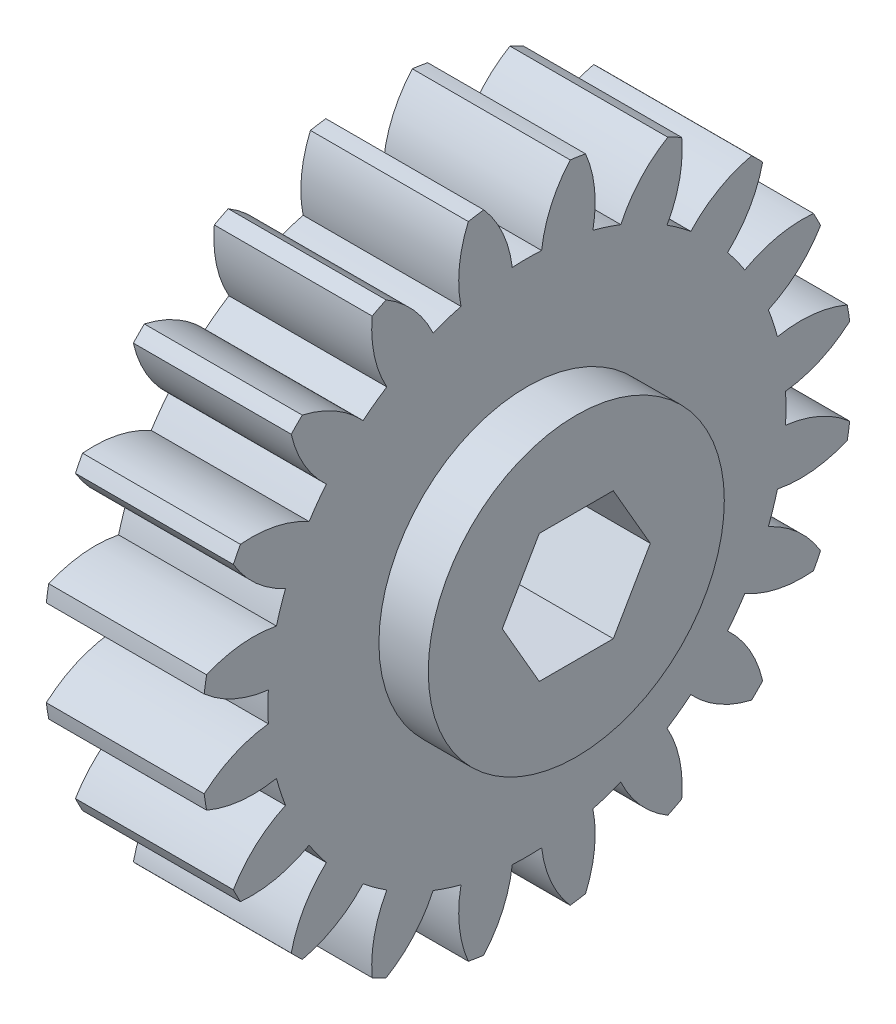
SolidWorks part; units mm, degrees
ref_plane "Plane1" through (0, 0, 0) normal (0, 0, 1) x (1, 0, 0)
ref_plane "Plane2" through (0, 0, 0) normal (0, 1, 0) x (1, 0, 0)
ref_plane "Plane3" through (0, 0, 0) normal (1, 0, 0) x (0, 0, -1)
sketch "HoldingSke" plane through (0, 0, 0) normal (0, 1, 0) x (1, 0, 0)
  line L0 (0, 0) -> (0.6265, -0.228)
  line L1 (-15, 0) -> (100, 0) construction
  line L2 (0, 0) -> (-2.1039, 2.3779)
  line L3 (0, 0) -> (-11.863, 4.5341)
  line L4 (0, 0) -> (8.1152, 2.9537)
  line L5 (0, 0) -> (-46.8476, -17.4728)
  line L6 (0, 0) -> (-9.9476, -6.7116)
  line L7 (-2.1039, 2.3779) -> (8.6586, 51.2059)
  line L8 (-76.2, 54.61) -> (-75.3, 54.61)
  line L9 (-71.009, 38.7566) -> (-53.1078, 45.2721)
  line L10 (-76.2, 71.12) -> (104.1128, 71.12)
  line L11 (0, 0) -> (-12, 0)
  line L12 (-76.2, 101.6) -> (-76.147, 101.6)
  line L13 (24.9733, 27.94) -> (52.9518, 28.4284)
  line L14 (24.9733, 27.94) -> (24.9743, 27.94)
  line L15 (24.9733, 27.94) -> (100.4006, 29.5858)
  line L16 (-63.627, -1.5) -> (-12.827, -1.5)
  circle A0 centre (0, 0) radius 2.5
  circle A1 centre (0, 0) radius 13.124
  circle A2 centre (0, 0) radius 37.5
  circle A3 centre (0, 0) radius 2.5
  dimension "MHD" = 26.248
  dimension "Hub_dia" = 75
  dimension "Bore" = 5
  dimension "MBD" = 5
  dimension "Num_teeth" = 20
  dimension "Pitch" = 0.6667
  dimension "Overall_len" = 50
  dimension "Show_teeth" = 20
  dimension "Thickness" = 12
  dimension "OAL" = 50.0001
  dimension "T_dim" = 0.9
  dimension "Ap" = 20
  dimension "H" = 19.05
  dimension "Pitch_radius" = 180.3128
  dimension "Width" = 12
  dimension "Backlash" = 0.053
  dimension "Addendum_fac" = 1
  dimension "Dedendum_fac" = 1.25
  dimension "Clearance_fac" = 0.25
  dimension "Dedendum_add" = 0.001
  dimension "Module" = 1.5
sketch "BasProSke" plane through (0, 0, 0) normal (0, 1, 0) x (1, 0, 0)
  line L0 (-10, 0) -> (60, 0) construction
  line L1 (0, 0) -> (0, 16.5)
  line L2 (0, 0) -> (8, 0)
  line L3 (8, 0) -> (8, 16.5)
  line L4 (8, 16.5) -> (0, 16.5)
  dimension "Thickness" = 8
  dimension "Diameter" = 33
revolve "Base-Revolve" add sketch "BasProSke" angle 360 about L0
sketch "TooCutSke" plane through (0, 0, 0) normal (1, 0, 0) x (0, 0, -1)
  line L1 (0, 0) -> (0, 107) construction
  line L2 (0, 0) -> (-1.2696, 14.9462) construction
  line L3 (0, 0) -> (-4.6808, 29.5532) construction
  line L4 (-1.2696, 14.9462) -> (-2.3404, 14.7766) construction
  arc A0 (0.7438, 13.1029) -> (-0.7438, 13.1029) centre (0, 0) ccw
  arc A1 (2.21, 16.377) -> (-2.21, 16.377) centre (0, 0) ccw
  circle A2 centre (0, 0) radius 15 construction
  circle A3 centre (0, 0) radius 14.0954 construction
  arc A4 (-0.7438, 13.1029) -> (-2.21, 16.377) centre (-6.7025, 12.3999) ccw
  arc A5 (2.21, 16.377) -> (0.7438, 13.1029) centre (6.7025, 12.3999) ccw
  dimension "Root_dia" = 26.248
  dimension "Overcut_dia" = 33.0508
  dimension "Pitch_dia" = 30
  dimension "Base_dia" = 28.1908
  dimension "Flank_rad" = 6
  dimension "Half_ang" = 9
  dimension "Half_CT" = 1.0841
extrude "ToothCut" cut sketch "TooCutSke" along normal through all
fillet "Breaks" [suppressed] radius 0.03 tangent propagation no
fillet "RootFillets" [suppressed] radius 0.376
pattern_circular "TeethCuts" count 20 every 18 about axis through (-10, 0, 0) along (1, 0, 0) of "ToothCut", "RootFillets", "Breaks"
sketch "HubNeaOneSke" plane through (0, 0, 0) normal (-1, 0, 0) x (0, 0, 1)
  circle A0 centre (0, 0) radius 13.124
  dimension "Diameter" = 26.248
extrude "HubNearOne" [suppressed] add sketch "HubNeaOneSke" along normal blind 42.0001
sketch "HubNeaBotSke" plane through (0, 0, 0) normal (-1, 0, 0) x (0, 0, 1)
  circle A0 centre (0, 0) radius 13.124
  dimension "Diameter" = 26.248
extrude "HubNearBoth" [suppressed] add sketch "HubNeaBotSke" along normal blind 21
ref_plane "FarPln" through (8, 0, 0) normal (1, 0, 0) x (0, 0, -1)
sketch "HubFarSke" plane through (8, 0, 0) normal (1, 0, 0) x (0, 0, -1)
  circle A0 centre (0, 0) radius 13.124
  dimension "Diameter" = 26.248
extrude "HubFar" [suppressed] add sketch "HubFarSke" along normal blind 21
sketch "BorSke" plane through (0, 0, 0) normal (1, 0, 0) x (0, 0, -1)
  circle A0 centre (0, 0) radius 2.5
  dimension "Diameter" = 5
extrude "Bore" cut sketch "BorSke" along normal mid plane 100.0001
sketch "KeySke" plane through (0, 0, 0) normal (1, 0, 0) x (0, 0, -1)
  line L0 (-1, 0) -> (-1, 3.4)
  line L1 (-1, 3.4) -> (1, 3.4)
  line L2 (1, 3.4) -> (1, 0)
  line L3 (0, 0) -> (0, 34) construction
  line L4 (-1, 0) -> (1, 0)
  dimension "Offset" = 3.4
  dimension "Width" = 2
extrude "Keyway" [suppressed] cut sketch "KeySke" along normal mid plane 100.0001
pattern_circular "Keyway2" [suppressed] count 2 every 90 about axis through (-10, 0, 0) along (1, 0, 0) reverse direction yes
sketch "Sketch1" plane through (8, 0, 0) normal (1, 0, 0) x (0, 0, -1)
  line L1 (3.75, 0) -> (1.875, 3.2476)
  line L2 (1.875, 3.2476) -> (-1.875, 3.2476)
  line L3 (-1.875, 3.2476) -> (-3.75, 0)
  line L4 (-3.75, 0) -> (-1.875, -3.2476)
  line L5 (-1.875, -3.2476) -> (1.875, -3.2476)
  line L6 (1.875, -3.2476) -> (3.75, 0)
  circle A0 centre (0, 0) radius 3.2476 construction
  circle A1 centre (0, 0) radius 3.75 construction
  dimension "D1" = 7.5
extrude "Cut-Extrude1" cut sketch "Sketch1" against normal through all
ref_plane "Plane4" through (8, 16.2303, -2.9711) normal (1, 0, 0) x (0, 0, -1)
sketch "Sketch2" plane through (8, 16.2303, -2.9711) normal (1, 0, 0) x (0, 0, -1)
  line L0 (-6.7211, -16.2303) -> (-4.8461, -19.4779) construction
  line L1 (-4.8461, -19.4779) -> (-1.0961, -19.4779) construction
  line L2 (-1.0961, -19.4779) -> (0.7789, -16.2303) construction
  line L3 (0.7789, -16.2303) -> (-1.0961, -12.9827) construction
  line L4 (-1.0961, -12.9827) -> (-4.8461, -12.9827) construction
  line L5 (-4.8461, -12.9827) -> (-6.7211, -16.2303) construction
  line L6 (-4.8461, -12.9827) -> (-6.7211, -16.2303)
  line L7 (-1.0961, -12.9827) -> (-4.8461, -12.9827)
  line L8 (0.7789, -16.2303) -> (-1.0961, -12.9827)
  line L9 (-1.0961, -19.4779) -> (0.7789, -16.2303)
  line L10 (-4.8461, -19.4779) -> (-1.0961, -19.4779)
  line L11 (-6.7211, -16.2303) -> (-4.8461, -19.4779)
  circle A0 centre (-2.9711, -16.2303) radius 7.5
  dimension "D1" = 15
extrude "Boss-Extrude1" add sketch "Sketch2" along normal blind 2.5
sketch "Sketch3" plane through (0, 0, 0) normal (-1, 0, 0) x (0, 0, 1)
  line L0 (1.875, 3.2476) -> (3.75, 0) construction
  line L1 (-1.875, 3.2476) -> (1.875, 3.2476) construction
  line L2 (-3.75, 0) -> (-1.875, 3.2476) construction
  line L3 (-1.875, -3.2476) -> (-3.75, 0) construction
  line L4 (1.875, -3.2476) -> (-1.875, -3.2476) construction
  line L5 (3.75, 0) -> (1.875, -3.2476) construction
  line L6 (3.75, 0) -> (1.875, -3.2476)
  line L7 (1.875, -3.2476) -> (-1.875, -3.2476)
  line L8 (-1.875, -3.2476) -> (-3.75, 0)
  line L9 (-3.75, 0) -> (-1.875, 3.2476)
  line L10 (-1.875, 3.2476) -> (1.875, 3.2476)
  line L11 (1.875, 3.2476) -> (3.75, 0)
  circle A0 centre (0, 0) radius 7.5
  dimension "D1" = 15
extrude "Boss-Extrude2" add sketch "Sketch3" along normal blind 2.5
equation "' \"Module@HoldingSke\" = 6.35"
equation "' \"Num_teeth@HoldingSke\" = 12"
equation "' \"Ap@HoldingSke\" =  20"
equation "' \"Ap@HoldingSke\" = 20"
equation "' \"Width@HoldingSke\" = 0.5 * 25.4"
equation "' \"Hub_dia@HoldingSke\"= 1 * 25.4"
equation "' \"Hub_dia@HoldingSke\" = 1 * 25.4"
equation "' \"Overall_len@HoldingSke\" = 1.0 * 25.4"
equation "' \"Bore@HoldingSke\" = 0.75 * 25.4"
equation "' \"T_dim@HoldingSke\" = 0.1 * 25.4"
equation "' \"Width@KeySke\" = 0.25 * 25.4"
equation "' \"Show_teeth@HoldingSke\" = 13"
equation "' \"Backlash@HoldingSke\" = 0.009 * 25.4"
equation "' \"Addendum_fac@HoldingSke\" = 1.0"
equation "' \"Dedendum_fac@HoldingSke\" = 1.25"
equation "' \"Dedendum_add@HoldingSke\" = 0.00005 * 25.4"
equation "' \"Clearance_fac@HoldingSke\" = 0.25"
equation "\"Pitch@HoldingSke\" = 1 / \"Module@HoldingSke\""
equation "\"Overcut_dia@TooCutSke\" = (\"Num_teeth@HoldingSke\" + 2 * \"Addendum_fac@HoldingSke\") / \"Pitch@HoldingSke\" + 0.002 * 25.4"
equation "\"Pitch_dia@TooCutSke\" = \"Num_teeth@HoldingSke\" / \"Pitch@HoldingSke\""
equation "\"Base_dia@TooCutSke\" = \"Num_teeth@HoldingSke\" / \"Pitch@HoldingSke\" * cos((\"Ap@HoldingSke\"  * 3.14159265 / 180))"
equation "\"Root_dia@TooCutSke\" = (\"Num_teeth@HoldingSke\" + 2) / \"Pitch@HoldingSke\" - 2 * (\"Addendum_fac@HoldingSke\" + \"Dedendum_fac@HoldingSke\") / \"Pitch@HoldingSke\" - \"Dedendum_add@HoldingSke\" * 2"
equation "\"Half_ang@TooCutSke\" = 180 / \"Num_teeth@HoldingSke\""
equation "\"Half_CT@TooCutSke\" = \"Num_teeth@HoldingSke\" / \"Pitch@HoldingSke\" * sin((3.14159265 / 2 / \"Num_teeth@HoldingSke\")) / 2 - 7 * \"Backlash@HoldingSke\" / 4"
equation "\"Flank_rad@TooCutSke\" = \"Num_teeth@HoldingSke\" / \"Pitch@HoldingSke\" / 5"
equation "\"Radius@RootFillets\" = \"Clearance_fac@HoldingSke\" / \"Pitch@HoldingSke\" + \"Dedendum_add@HoldingSke\""
equation "\"Break_rad@Breaks\" = 0.02 / \"Pitch@HoldingSke\""
equation "\"Thickness@HoldingSke\" = \"Width@HoldingSke\""
equation "\"OAL@HoldingSke\" = \"Thickness@HoldingSke\""
equation "\"MHD@HoldingSke\" = (\"Num_teeth@HoldingSke\" + 2) / \"Pitch@HoldingSke\" - 2 * (\"Addendum_fac@HoldingSke\" + \"Dedendum_fac@HoldingSke\")  / \"Pitch@HoldingSke\" - \"Dedendum_add@HoldingSke\" * 2"
equation "\"MBD@HoldingSke\" = (\"Num_teeth@HoldingSke\" + 2) / \"Pitch@HoldingSke\" - 2 * (\"Addendum_fac@HoldingSke\" + \"Dedendum_fac@HoldingSke\")  / \"Pitch@HoldingSke\" - \"Dedendum_add@HoldingSke\" * 2 - 0.002 * 25.4"
equation "\"MHD@HoldingSke\" = ((sgn( \"MHD@HoldingSke\" - \"Hub_dia@HoldingSke\" )-1)*( \"MHD@HoldingSke\" - \"Hub_dia@HoldingSke\" ))/-2+ \"Hub_dia@HoldingSke\""
equation "\"MBD@HoldingSke\" = ((sgn( \"MBD@HoldingSke\" - \"Bore@HoldingSke\" )-1)*( \"MBD@HoldingSke\" - \"Bore@HoldingSke\" ))/-2+ \"Bore@HoldingSke\""
equation "\"OAL@HoldingSke\" = ((sgn( \"OAL@HoldingSke\" - \"Overall_len@HoldingSke\" )+1)*( \"OAL@HoldingSke\" - \"Overall_len@HoldingSke\" ))/2 + \"Overall_len@HoldingSke\" + 0.000002 * 25.4"
equation "\"Num_teeth@TeethCuts\" = int( \"Show_teeth@HoldingSke\" ) + 1"
equation "\"Num_teeth@TeethCuts\" = ((sgn( \"Num_teeth@TeethCuts\" - \"Num_teeth@HoldingSke\" )-1)*( \"Num_teeth@TeethCuts\" - \"Num_teeth@HoldingSke\" ))/-2+ \"Num_teeth@HoldingSke\""
equation "\"Num_teeth@TeethCuts\" = ((sgn( \"Num_teeth@TeethCuts\" - 2.0)+1)*( \"Num_teeth@TeethCuts\" - 2.0))/2 +2.0"
equation "\"Angle@TeethCuts\" = 360.0 / \"Num_teeth@HoldingSke\""
equation "\"Diameter@BasProSke\" = (\"Num_teeth@HoldingSke\" + 2 * \"Addendum_fac@HoldingSke\") / \"Pitch@HoldingSke\""
equation "\"Thickness@BasProSke\"=8"
equation "' \"Fillet_rad@BasProSke\" =  \"Thickness@HoldingSke\" * 0.05"
equation "' \"Fillet_rad@BasProSke\" = \"Thickness@HoldingSke\" * 0.05"
equation "\"MHD@HoldingSke\" = ((sgn( \"MHD@HoldingSke\" - \"Root_dia@TooCutSke\" )-1)*( \"MHD@HoldingSke\" - \"Root_dia@TooCutSke\" ))/-2+ \"Root_dia@TooCutSke\""
equation "\"Diameter@HubNeaOneSke\" = \"MHD@HoldingSke\""
equation "\"Length@HubNearOne\" = \"OAL@HoldingSke\" - \"Thickness@BasProSke\""
equation "\"Diameter@HubNeaBotSke\" = \"MHD@HoldingSke\""
equation "\"Length@HubNearBoth\" = ( \"OAL@HoldingSke\" - \"Thickness@BasProSke\" ) / 2.0"
equation "\"Thickness@FarPln\" = \"Thickness@BasProSke\""
equation "\"Diameter@HubFarSke\" = \"MHD@HoldingSke\""
equation "\"Length@HubFar\" = ( \"OAL@HoldingSke\" - \"Thickness@BasProSke\" ) / 2.0"
equation "\"Diameter@BorSke\" = \"MBD@HoldingSke\""
equation "\"D1@Bore\" = \"OAL@HoldingSke\" * 2.0"
equation "\"D1@Keyway\" = \"OAL@HoldingSke\" * 2.0"
equation "\"Offset@KeySke\" = \"T_dim@HoldingSke\" + \"MBD@HoldingSke\" / 2.0"
